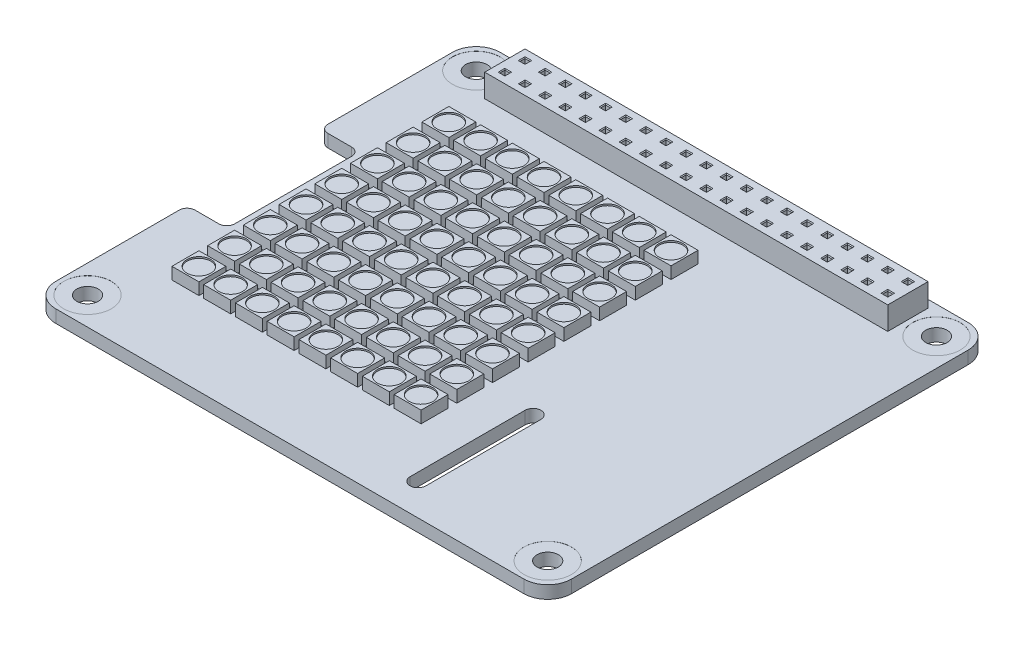
SolidWorks part; units mm, degrees
material "Silicon"
ref_plane "Front Plane" through (0, 0, 0) normal (0, 0, 1) x (1, 0, 0)
ref_plane "Top Plane" through (0, 0, 0) normal (0, 1, 0) x (1, 0, 0)
ref_plane "Right Plane" through (0, 0, 0) normal (1, 0, 0) x (0, 0, -1)
sketch "BaseS" plane through (0, 0, 0) normal (0, 1, 0) x (1, 0, 0)
  line L1 (-42.5, 28) -> (42.5, 28)
  line L2 (-42.5, 28) -> (-42.5, -28)
  line L3 (-42.5, -28) -> (42.5, -28)
  line L4 (42.5, 28) -> (42.5, -28)
  line L5 (-42.5, 28) -> (42.5, -28) construction
  line L6 (-42.5, -28) -> (42.5, 28) construction
  point P0 (0, 0)
  dimension "Width" = 56
  dimension "Length" = 85
extrude "Base" add sketch "BaseS" along normal mid plane 1.6
hole_wizard "M2.5 Clearance Hole" positions "Sketch2" profile "Sketch3" hole size "M2.5" standard "ANSI Metric" end condition through all
sketch "Sketch2" plane through (0, 0.8, 0) normal (0, 1, 0) x (1, 0, 0)
  line L0 (-39, 24.5) -> (-39, -24.5) construction
  line L2 (-42.5, 28) -> (-42.5, -28) construction
  line L3 (42.5, 28) -> (-42.5, 28) construction
  line L4 (-42.5, -28) -> (42.5, -28) construction
  point P0 (-39, 24.5)
  point P2 (-39, -24.5)
  dimension "XDim" = 3.5
  dimension "YDim" = 3.5
  dimension "D3" = 3.5
sketch "Sketch3" plane through (-39, 0.8, -24.5) normal (1, 0, 0) x (0, 0, 1)
  line L0 (0, 0) -> (0, 1.6)
  line L1 (0, 1.6) -> (1.35, 1.6)
  line L2 (1.35, 1.6) -> (1.35, 0)
  line L5 (1.35, 0) -> (0, 0)
  line L11 (0, -6.35) -> (0, 107.95) construction
  dimension "Thru Hole Dia." = 2.7
  dimension "Thru Hole Depth" = 1.6
sketch "FastenerAreaS" plane through (0, 0.8, 0) normal (0, 1, 0) x (1, 0, 0)
  circle A0 centre (-39, -24.5) radius 3
  circle A1 centre (-39, -24.5) radius 1.35 construction
  circle A2 centre (-39, -24.5) radius 1.35
  circle A3 centre (-39, 24.5) radius 1.35 construction
  circle A4 centre (-39, 24.5) radius 1.35
  circle A5 centre (-39, 24.5) radius 3
  dimension "RefDia" = 6
  dimension "DiaControl" = 1.65
extrude "FastenerArea" cut sketch "FastenerAreaS" against normal blind 0.01
pattern_linear "HLP FastenerHoles" count 2 spacing 58 along (1, 0, 0) of "M2.5 Clearance Hole", "FastenerArea"
mirror "VM FA" about plane through (0, 0, 0) normal (0, 1, 0) of "HLP FastenerHoles", "FastenerArea"
hole_wizard "Ø1.0 (1) Diameter Hole IO" positions "Sketch7" profile "Sketch8" hole size "Ø1.0" standard "ANSI Metric" end condition through all
sketch "Sketch7" plane through (0, 0.8, 0) normal (0, 1, 0) x (1, 0, 0)
  circle A0 centre (-39, 24.5) radius 1.35 construction
  point P0 (-34.13, 25.77)
  dimension "YDim" = 1.27
  dimension "XDim" = 4.87
sketch "Sketch8" plane through (-34.13, 0.8, -25.77) normal (1, 0, 0) x (0, 0, 1)
  line L0 (0, 0) -> (0, 1.6)
  line L1 (0, 1.6) -> (0.5, 1.6)
  line L2 (0.5, 1.6) -> (0.5, 0)
  line L5 (0.5, 0) -> (0, 0)
  line L11 (0, -6.35) -> (0, 107.95) construction
  dimension "Thru Hole Dia." = 1
  dimension "Thru Hole Depth" = 1.6
pattern_linear "LP DiaHole IO" count 20 spacing 2.54 along (1, 0, 0) count 2 spacing 2.54 along (0, 0, 1) of "Ø1.0 (1) Diameter Hole IO"
fillet "CornerRadius" radius 3 4 edges at (42.5, 0, -28) (42.5, 0, 28) (-42.5, 0, -28) (-42.5, 0, 28)
sketch "Sketch9" plane through (0, 0.8, 0) normal (0, 1, 0) x (1, 0, 0)
  line L0 (22.5, 28) -> (22.5, -28)
  line L1 (39.5, 28) -> (-39.5, 28) construction
  line L2 (-39.5, -28) -> (39.5, -28) construction
  line L3 (-42.5, 25) -> (-42.5, -25) construction
  line L4 (42.5, -25) -> (42.5, 25) construction
  line L5 (22.5, -28) -> (39.5, -28)
  line L6 (42.5, -25) -> (42.5, 25)
  line L7 (39.5, 28) -> (22.5, 28)
  arc A0 (39.5, -28) -> (42.5, -25) centre (39.5, -25) ccw construction
  arc A1 (42.5, 25) -> (39.5, 28) centre (39.5, 25) ccw construction
  arc A2 (39.5, -28) -> (42.5, -25) centre (39.5, -25) ccw
  arc A3 (42.5, 25) -> (39.5, 28) centre (39.5, 25) ccw
  dimension "D1" = 65
extrude "Cut-Extrude1" cut sketch "Sketch9" against normal through all
fillet "Fillet1" radius 3 2 edges at (22.5, 0, 28) (22.5, 0, -28)
sketch "Sketch10" plane through (0, 0.8, 0) normal (0, 1, 0) x (1, 0, 0)
  line L0 (-42.5, 8.3) -> (-37.5, 8.3)
  line L1 (-42.5, 25) -> (-42.5, -25) construction
  line L2 (-37.5, 8.3) -> (-37.5, -8.45)
  line L3 (-37.5, -8.45) -> (-42.5, -8.45)
  line L4 (-42.5, -8.45) -> (-42.5, 8.3)
  dimension "D1" = 5
  dimension "D2" = 16.75
  dimension "D3" = 8.3
extrude "Cut-Extrude2" cut sketch "Sketch10" against normal through all
fillet "Fillet2" radius 1 4 edges at (-42.5, 0, 8.45) (-37.5, 0, 8.45) (-37.5, 0, -8.3) (-42.5, 0, -8.3)
sketch "Sketch11" plane through (0, 0.8, 0) normal (0, 1, 0) x (1, 0, 0)
  line L0 (2.15, -9.5) -> (2.15, -24) construction
  line L1 (3.15, -9.5) -> (3.15, -24)
  line L2 (1.15, -9.5) -> (1.15, -24)
  line L3 (22.5, 25) -> (22.5, -25) construction
  line L4 (-39.5, -28) -> (19.5, -28) construction
  arc A0 (3.15, -9.5) -> (1.15, -9.5) centre (2.15, -9.5) ccw
  arc A1 (1.15, -24) -> (3.15, -24) centre (2.15, -24) ccw
  point P2 (2.15, -16.75)
  dimension "D1" = 20.35
  dimension "D2" = 1
  dimension "D3" = 14.5
  dimension "D4" = 11.25
extrude "Cut-Extrude3" cut sketch "Sketch11" against normal through all
sketch "Sketch12" plane through (0, -0.8, 0) normal (0, -1, 0) x (1, 0, 0)
  line L0 (-35.4, -27.04) -> (-35.4, -21.96)
  line L1 (-35.4, -21.96) -> (15.4, -21.96)
  line L2 (15.4, -21.96) -> (15.4, -27.04)
  line L3 (15.4, -27.04) -> (-35.4, -27.04)
  circle A0 centre (-39, -24.5) radius 1.35 construction
  dimension "D1" = 5.08
  dimension "D2" = 50.8
  dimension "D3" = 3.6
  dimension "D4" = 2.54
extrude "Boss-Extrude1" add sketch "Sketch12" along normal blind 5.8
sketch "Sketch14" plane through (0, -6.6, 0) normal (0, -1, 0) x (1, 0, 0)
  line L0 (-35.4, -27.04) -> (15.4, -27.04) construction
  line L1 (14.45, -25.45) -> (13.81, -25.45)
  line L2 (14.45, -25.45) -> (14.45, -26.09)
  line L3 (14.45, -26.09) -> (13.81, -26.09)
  line L4 (13.81, -25.45) -> (13.81, -26.09)
  line L5 (14.45, -25.45) -> (13.81, -26.09) construction
  line L6 (14.45, -26.09) -> (13.81, -25.45) construction
  line L7 (15.4, -27.04) -> (15.4, -21.96) construction
  point P0 (14.13, -25.77)
  dimension "D1" = 0.64
  dimension "D2" = 0.64
  dimension "D3" = 0.95
  dimension "D4" = 0.95
extrude "Cut-Extrude4" cut sketch "Sketch14" against normal blind 5.8
chamfer "Chamfer1" distance 0.3 angle 45 4 edges at (14.13, -6.6, -25.45) (14.45, -6.6, -25.77) (13.81, -6.6, -25.77) (14.13, -6.6, -26.09)
pattern_linear "LPattern1" count 20 spacing 2.54 along (-1, 0, 0) count 2 spacing 2.54 along (0, 0, 1) of "Chamfer1", "Cut-Extrude4"
sketch "Sketch15" plane through (0, 0.8, 0) normal (0, 1, 0) x (1, 0, 0)
  line L0 (15.4, 21.96) -> (15.4, 27.04)
  line L1 (15.4, 27.04) -> (-35.4, 27.04)
  line L2 (-35.4, 27.04) -> (-35.4, 21.96)
  line L3 (-35.4, 21.96) -> (15.4, 21.96)
  circle A0 centre (-39, 24.5) radius 1.35 construction
  dimension "D1" = 5.08
  dimension "D2" = 50.8
  dimension "D3" = 3.6
  dimension "D4" = 2.54
extrude "Boss-Extrude2" add sketch "Sketch15" along normal blind 2.9
sketch "Sketch16" plane through (0, 3.7, 0) normal (0, 1, 0) x (1, 0, 0)
  line L0 (15.4, 27.04) -> (-35.4, 27.04) construction
  line L1 (-33.81, 26.09) -> (-34.45, 26.09)
  line L2 (-33.81, 26.09) -> (-33.81, 25.45)
  line L3 (-33.81, 25.45) -> (-34.45, 25.45)
  line L4 (-34.45, 26.09) -> (-34.45, 25.45)
  line L5 (-33.81, 26.09) -> (-34.45, 25.45) construction
  line L6 (-33.81, 25.45) -> (-34.45, 26.09) construction
  line L7 (-35.4, 27.04) -> (-35.4, 21.96) construction
  point P0 (-34.13, 25.77)
  dimension "D1" = 0.64
  dimension "D2" = 0.64
  dimension "D3" = 0.95
  dimension "D4" = 0.95
extrude "Cut-Extrude5" cut sketch "Sketch16" against normal blind 2.9
chamfer "Chamfer2" distance 0.1 angle 45 4 edges at (-33.81, 3.7, -25.77) (-34.13, 3.7, -26.09) (-34.45, 3.7, -25.77) (-34.13, 3.7, -25.45)
pattern_linear "LPattern2" count 20 spacing 2.54 along (1, 0, 0) count 2 spacing 2.54 along (0, 0, 1) of "Chamfer2", "Cut-Extrude5"
sketch "Sketch17" plane through (0, 0.8, 0) normal (0, 1, 0) x (1, 0, 0)
  line L0 (-35.32, 17.36) -> (-35.32, 13.96)
  line L5 (-35.32, 13.96) -> (-31.92, 13.96)
  line L6 (-31.92, 13.96) -> (-31.92, 17.36)
  line L7 (-31.92, 17.36) -> (-35.32, 17.36)
  line L8 (-35.4, 21.96) -> (15.4, 21.96) construction
  line L9 (-42.5, 25) -> (-42.5, 9.3) construction
  dimension "D1" = 3.4
  dimension "D2" = 3.4
  dimension "D3" = 4.6
  dimension "D4" = 7.18
extrude "Boss-Extrude3" add sketch "Sketch17" along normal blind 1.5
sketch "Sketch18" plane through (0, 2.3, 0) normal (0, 1, 0) x (1, 0, 0)
  line L0 (-35.32, 17.36) -> (-31.92, 13.96) construction
  line L1 (-31.92, 17.36) -> (-35.32, 13.96) construction
  line L2 (-35.32, 13.96) -> (-31.92, 13.96) construction
  line L3 (-35.32, 17.36) -> (-35.32, 13.96) construction
  circle A1 centre (-33.62, 15.66) radius 1.5
  dimension "D1" = 3
extrude "Cut-Extrude6" cut sketch "Sketch18" against normal blind 0.2
pattern_linear "LPattern3" count 8 spacing 4.5 along (0, 0, 1) count 8 spacing 4 along (1, 0, 0) of "Boss-Extrude3", "Cut-Extrude6"
